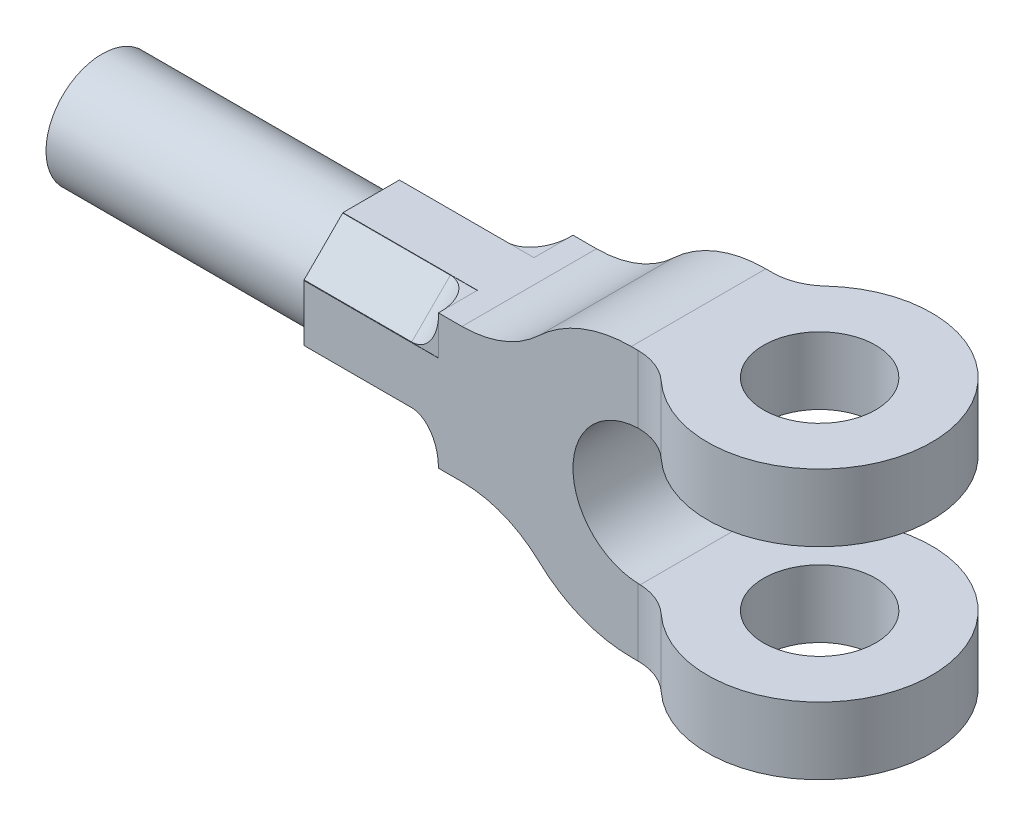
SolidWorks part; units mm, degrees
ref_plane "Front Plane" through (0, 0, 0) normal (1, 0, 0) x (0, 1, 0)
ref_plane "Top Plane" through (0, 0, 0) normal (0, 0, 1) x (0, 1, 0)
ref_plane "Right Plane" through (0, 0, 0) normal (0, 1, 0) x (-1, 0, 0)
sketch "Sketch2" plane through (0, 0, 0) normal (0, 0, 1) x (0, 1, 0)
  line L1 (0, 0) -> (-120, 0)
  line L2 (0, 0) -> (0, 250)
  line L3 (0, 250) -> (-120, 250)
  line L4 (-120, 0) -> (-120, 250)
  dimension "D1" = 120
  dimension "D2" = 250
extrude "Boss-Extrude1" add sketch "Sketch2" along normal blind 100
sketch "Sketch3" plane through (0, 0, 100) normal (0, 0, 1) x (1, 0, 0)
  line L0 (-250, -60) -> (0, -60) construction
  line L1 (-250, 0) -> (-250, -120) construction
  line L2 (0, -120) -> (0, 0) construction
  line L3 (-250, -90) -> (-179.4983, -90)
  line L4 (-250, -30) -> (-179.4983, -30)
  line L5 (-100, -90) -> (0, -90)
  line L6 (-100, -30) -> (0, -30)
  arc A0 (-100, -30) -> (-100, -90) centre (-100, -60) ccw
  arc A1 (-145.1809, -103.6364) -> (-145.1809, -16.3636) centre (-104, -60) ccw
  arc A2 (-145.1809, -16.3636) -> (-179.4983, -30) centre (-179.4983, 20) cw
  arc A3 (-145.1809, -103.6364) -> (-179.4983, -90) centre (-179.4983, -140) ccw
  point P15 (-155.9615, -30)
  point P18 (-155.9615, -90)
  line M3 (0, 0) -> (-250, 0)
  line M4 (-250, 0) -> (-250, -120)
  line M5 (-250, -120) -> (0, -120)
  line M6 (0, -120) -> (0, 0)
  dimension "D1" = 60
  dimension "D2" = 120
  dimension "D6" = 50
  dimension "D3" = 4
  dimension "D4" = 150
  dimension "D5" = 30
extrude "Cut-Extrude1" cut sketch "Sketch3" against normal through all contours A1 A3 L3 M4 M5 | A2 A1 L4 M3 M4 | L0 A0 L5 A1 | A0 L0 A1 L6 | L0 A1 L5 M6 | A1 L0 L6 M6 region at (-85.3374, -45.9515, 100) region at (-85.3374, -74.0485, 100) region at (-195.5027, -13.8252, 100) region at (-195.5027, -106.1748, 100) region at (-23.362, -44.5752, 100) region at (-23.362, -75.4248, 100)
sketch "Sketch4" plane through (0, 0, 0) normal (0, 1, 0) x (-1, 0, 0)
  line L0 (0, 100) -> (104, 100) construction
  line L1 (0, 100) -> (0, 0) construction
  line L2 (0, 0) -> (104, 0) construction
  line L3 (50, 50) -> (250, 50) construction
  line L4 (250, 0) -> (250, 100) construction
  line L6 (250, 80) -> (100.9902, 80)
  line L7 (250, 80) -> (250, 20)
  line L8 (250, 20) -> (100.9902, 20)
  arc A0 (83.9935, 86.6667) -> (83.9935, 13.3333) centre (50, 50) ccw
  circle A1 centre (50, 50) radius 25
  arc A2 (100.9902, 20) -> (83.9935, 13.3333) centre (100.9902, -5) ccw
  arc A3 (100.9902, 80) -> (83.9935, 86.6667) centre (100.9902, 105) cw
  dimension "D1" = 50
  dimension "D3" = 25
  dimension "D2" = 60
extrude "Cut-Extrude2" cut sketch "Sketch4" against normal through all flip side to cut
sketch "Sketch5" plane through (-250, 0, 0) normal (-1, 0, 0) x (0, -1, 0)
  line L0 (90, 62.6) -> (72.6, 80)
  line L1 (90, 20) -> (90, 80) construction
  line L2 (90, 80) -> (30, 80) construction
  line L3 (72.6, 80) -> (90, 80)
  line L4 (90, 80) -> (90, 62.6)
  line L5 (90.0082, 20.0082) -> (72.6082, 20.0082)
  line L6 (72.6082, 20.0082) -> (90.0082, 37.4082)
  line L7 (90.0082, 37.4082) -> (90.0082, 20.0082)
  line L8 (30.0163, 20) -> (30.0163, 37.4)
  line L9 (30.0163, 37.4) -> (47.4163, 20)
  line L10 (47.4163, 20) -> (30.0163, 20)
  line L11 (30.0082, 79.9918) -> (47.4082, 79.9918)
  line L12 (47.4082, 79.9918) -> (30.0082, 62.5918)
  line L13 (30.0082, 62.5918) -> (30.0082, 79.9918)
  circle A0 centre (60.0082, 50) radius 25
  dimension "D1" = 50
  dimension "D2" = 17.4
  dimension "D3" = 17.4
  dimension "D4" = 4
extrude "Cut-Extrude6" cut sketch "Sketch5" against normal blind 60 contours L13 L12 L11 | L0 L5 | L6 L5 | L9 L8 L2 region at (-250, -84.2, 74.2) region at (-250, -84.2082, 25.8082) region at (-250, -35.8163, 25.8) region at (-250, -35.8082, 74.1918)
extrude "Boss-Extrude3" add sketch "Sketch5<4>" along normal blind 120 contours A0 region at (-250, -60.0082, 50)
sketch "Sketch5<4>" plane through (-250, 0, 0) normal (-1, 0, 0) x (0, -1, 0) same geometry as "Sketch5"
sketch "Sketch6" plane through (0, -30, 0) normal (0, 1, 0) x (1, 0, 0)
  line L1 (-250, -80) -> (-190, -80)
  line L2 (-250, -80) -> (-250, -62.6)
  line L3 (-250, -62.6) -> (-190, -62.6)
  line L4 (-190, -80) -> (-190, -62.6)
  line L5 (-250, -20) -> (-190, -20)
  line L6 (-250, -20) -> (-250, -37.4)
  line L7 (-250, -37.4) -> (-190, -37.4)
  line L8 (-190, -20) -> (-190, -37.4)
  dimension "D1" = 60
  dimension "D2" = 17.4
  dimension "D3" = 60
  dimension "D4" = 17.4
extrude "Cut-Extrude7" cut sketch "Sketch6" against normal blind 0.1
sketch "Sketch7" plane through (0, 0, 20) normal (0, 0, -1) x (-1, 0, 0)
  line L1 (250, -90) -> (190, -90)
  line L2 (250, -90) -> (250, -72.6)
  line L3 (250, -72.6) -> (190, -72.6)
  line L4 (190, -90) -> (190, -72.6)
  dimension "D1" = 60
  dimension "D2" = 17.4
extrude "Cut-Extrude8" cut sketch "Sketch7" against normal blind 0.1
sketch "Sketch8" plane through (0, 0, 80) normal (0, 0, 1) x (1, 0, 0)
  line L1 (-250, -30.1) -> (-190, -30.1)
  line L2 (-250, -30.1) -> (-250, -47.5)
  line L3 (-250, -47.5) -> (-190, -47.5)
  line L4 (-190, -30.1) -> (-190, -47.5)
  dimension "D1" = 60
  dimension "D2" = 17.4
extrude "Cut-Extrude9" cut sketch "Sketch8" against normal blind 0.1
fillet "Fillet5" radius 12 1 edges at (-190, -38.7082, 71.2918)
fillet "Fillet6" radius 12 3 edges at (-190, -81.3, 71.3) (-190, -81.35, 28.75) (-190, -38.7582, 28.6582)
